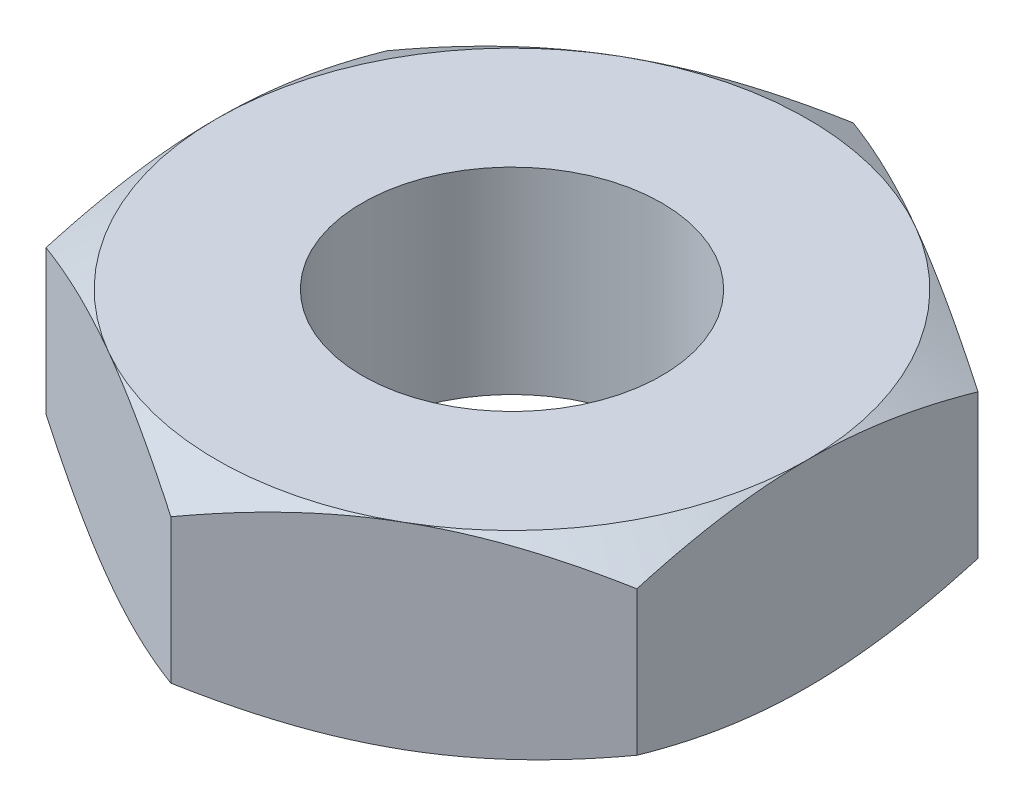
SolidWorks part; units mm, degrees
ref_plane "Front Plane" through (0, 0, 0) normal (0, 0, 1) x (1, 0, 0)
ref_plane "Top Plane" through (0, 0, 0) normal (0, 1, 0) x (1, 0, 0)
ref_plane "Right Plane" through (0, 0, 0) normal (1, 0, 0) x (0, 0, -1)
sketch "Sketch1" plane through (0, 0, 0) normal (0, 1, 0) x (1, 0, 0)
  line L1 (-4.7625, 2.7496) -> (-4.7625, -2.7496)
  line L2 (-4.7625, -2.7496) -> (0, -5.4993)
  line L3 (0, -5.4993) -> (4.7625, -2.7496)
  line L4 (4.7625, -2.7496) -> (4.7625, 2.7496)
  line L5 (4.7625, 2.7496) -> (0, 5.4993)
  line L6 (0, 5.4993) -> (-4.7625, 2.7496)
  circle A0 centre (0, 0) radius 4.7625 construction
  circle A1 centre (0, 0) radius 2.413
  dimension "Thread Size" = 4.826
  dimension "Hex" = 9.525
extrude "Boss-Extrude1" add sketch "Sketch1" along normal mid plane 3.175
sketch "Sketch2" plane through (0, 1.5875, 0) normal (0, 1, 0) x (1, 0, 0)
  circle A0 centre (0, 0) radius 2.413 construction
  circle A1 centre (0, 0) radius 2.413
curve "Helix/Spiral1" [suppressed] pitch 1.0583 height 4.2333 turns 4 parameters "Pitch"=1.0583
sketch "Sketch3" plane through (0, 0, 0) normal (1, 0, 0) x (0, 0, -1)
  line L0 (1.7256, 2.1167) -> (2.413, 2.5135)
  line L1 (2.413, 2.5135) -> (2.413, 1.5875)
  line L2 (2.413, 1.5875) -> (1.7256, 1.9844)
  line L3 (1.7256, 1.9844) -> (1.7256, 2.1167)
  line L4 (2.0693, 2.3151) -> (2.0693, 1.7859) construction
  line L5 (1.7256, 2.0505) -> (2.413, 2.0505) construction
  line L6 (2.413, 1.5875) -> (-2.413, 1.5875) construction
  dimension "D1" = 60
  dimension "D2" = 0.1323
  dimension "D3" = 0.5292
sweep "Sweep1" [suppressed] add profiles "Sketch3" path "Helix/Spiral1"
sketch "Sketch4" plane through (0, 1.5875, 0) normal (0, 1, 0) x (1, 0, 0)
  circle A1 centre (0, 0) radius 2.413
  circle A2 centre (0, 0) radius 2.413
  dimension "D1" = 0
extrude "Cut-Extrude1" [suppressed] cut sketch "Sketch4" along normal through all and the other way through all draft 45
sketch "Sketch5" plane through (0, 1.5875, 0) normal (0, 1, 0) x (1, 0, 0)
  circle A0 centre (0, 0) radius 4.7625 construction
  circle A1 centre (0, 0) radius 4.7625
extrude "Cut-Extrude2" cut sketch "Sketch5" against normal through all draft 60 flip side to cut
mirror "Mirror1" about plane through (0, 0, 0) normal (0, 1, 0) of "Cut-Extrude2", "Cut-Extrude1"
equation "\"D2@Sketch3\" = \"Pitch@Helix/Spiral1\"*.125"
equation "\"D3@Sketch3\" = \"Pitch@Helix/Spiral1\"*.5"
equation "\"D3@Helix/Spiral1\" = \"Height@Boss-Extrude1\"+\"Pitch@Helix/Spiral1\""
